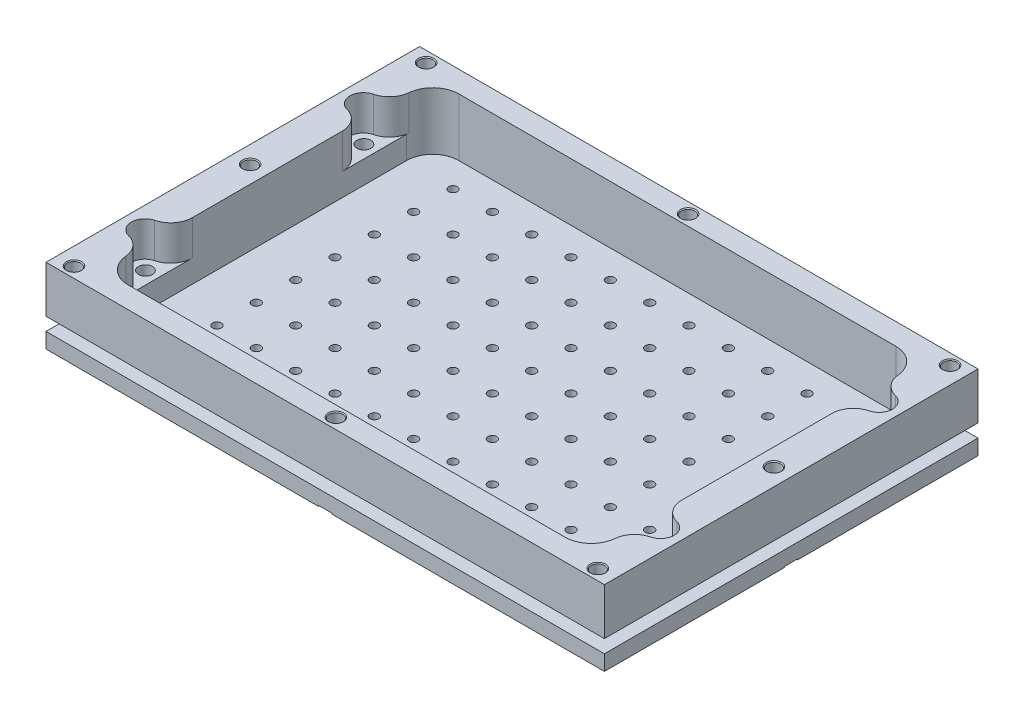
SolidWorks part; units mm, degrees
material "Alliage 6061"
ref_plane "Plan de face" through (0, 0, 0) normal (0, 0, 1) x (1, 0, 0)
ref_plane "Plan de dessus" through (0, 0, 0) normal (0, 1, 0) x (1, 0, 0)
ref_plane "Plan de droite" through (0, 0, 0) normal (1, 0, 0) x (0, 0, -1)
sketch "Esquisse1" plane through (0, 0, 0) normal (0, 1, 0) x (1, 0, 0)
  line L1 (-63.88, 42.74) -> (63.88, 42.74)
  line L2 (-63.88, 42.74) -> (-63.88, -42.74)
  line L3 (-63.88, -42.74) -> (63.88, -42.74)
  line L4 (63.88, 42.74) -> (63.88, -42.74)
  line L5 (-63.88, 42.74) -> (63.88, -42.74) construction
  line L6 (-63.88, -42.74) -> (63.88, 42.74) construction
  point P0 (0, 0)
  dimension "D1" = 85.48
  dimension "D2" = 127.76
extrude "Boss.-Extru.1" add sketch "Esquisse1" along normal blind 12
sketch "Esquisse2" plane through (0, 12, 0) normal (0, 1, 0) x (1, 0, 0)
  line L1 (-49.98, 37.84) -> (49.98, 37.84)
  line L2 (-55.98, 31.84) -> (-55.98, -31.84)
  line L3 (-49.98, -37.84) -> (49.98, -37.84)
  line L4 (55.98, 31.84) -> (55.98, -31.84)
  line L5 (-55.98, 37.84) -> (55.98, -37.84) construction
  line L6 (-55.98, -37.84) -> (55.98, 37.84) construction
  line L7 (-63.88, 42.74) -> (-63.88, -42.74) construction
  arc A0 (-55.98, -31.84) -> (-49.98, -37.84) centre (-49.98, -31.84) ccw
  arc A1 (49.98, -37.84) -> (55.98, -31.84) centre (49.98, -31.84) ccw
  arc A2 (49.98, 37.84) -> (55.98, 31.84) centre (49.98, 31.84) cw
  arc A3 (-49.98, 37.84) -> (-55.98, 31.84) centre (-49.98, 31.84) ccw
  point P0 (0, 0)
  dimension "D3" = 6
  dimension "D1" = 75.68
  dimension "D2" = 7.9
extrude "Enlèv. mat.-Extru.1" cut sketch "Esquisse2" against normal blind 8
ref_plane "Plan1" through (0, 3.5, 0) normal (0, -1, 0) x (-1, 0, 0)
sketch "Esquisse3" plane through (0, 3.5, 0) normal (0, -1, 0) x (-1, 0, 0)
  line L0 (63.88, 42.74) -> (63.88, -42.74) construction
  line L1 (-60.88, 39.74) -> (60.88, 39.74)
  line L2 (-60.88, 39.74) -> (-60.88, -39.74)
  line L3 (-60.88, -39.74) -> (60.88, -39.74)
  line L4 (60.88, 39.74) -> (60.88, -39.74)
  line L5 (-60.88, 39.74) -> (60.88, -39.74) construction
  line L6 (-60.88, -39.74) -> (60.88, 39.74) construction
  line L7 (-63.88, 42.74) -> (63.88, 42.74) construction
  point P0 (0, 0)
  dimension "D1" = 3
  dimension "D2" = 3
extrude "Enlèv. de mat.-Extru.-Mince1" cut sketch "Esquisse3" against normal blind 3 thin thin type one direction wall 10
sketch "Esquisse5" plane through (0, 12, 0) normal (0, 1, 0) x (1, 0, 0)
  line L2 (63.88, 42.74) -> (-63.88, 42.74) construction
  line L4 (-63.88, 42.74) -> (-63.88, -42.74) construction
  circle A0 centre (-45, 31.5) radius 1
  circle A1 centre (-36, 31.5) radius 1
  circle A2 centre (-27, 31.5) radius 1
  circle A3 centre (-18, 31.5) radius 1
  circle A4 centre (-9, 31.5) radius 1
  circle A5 centre (0, 31.5) radius 1
  circle A6 centre (9, 31.5) radius 1
  circle A7 centre (18, 31.5) radius 1
  circle A8 centre (27, 31.5) radius 1
  circle A9 centre (36, 31.5) radius 1
  circle A10 centre (45, 31.5) radius 1
  circle A12 centre (-36, 22.5) radius 1
  circle A13 centre (-27, 22.5) radius 1
  circle A14 centre (-18, 22.5) radius 1
  circle A15 centre (-9, 22.5) radius 1
  circle A16 centre (0, 22.5) radius 1
  circle A17 centre (9, 22.5) radius 1
  circle A18 centre (18, 22.5) radius 1
  circle A19 centre (27, 22.5) radius 1
  circle A20 centre (36, 22.5) radius 1
  circle A21 centre (45, 22.5) radius 1
  circle A23 centre (-36, 13.5) radius 1
  circle A24 centre (-27, 13.5) radius 1
  circle A25 centre (-18, 13.5) radius 1
  circle A26 centre (-9, 13.5) radius 1
  circle A27 centre (0, 13.5) radius 1
  circle A28 centre (9, 13.5) radius 1
  circle A29 centre (18, 13.5) radius 1
  circle A30 centre (27, 13.5) radius 1
  circle A31 centre (36, 13.5) radius 1
  circle A32 centre (45, 13.5) radius 1
  circle A34 centre (-36, 4.5) radius 1
  circle A35 centre (-27, 4.5) radius 1
  circle A36 centre (-18, 4.5) radius 1
  circle A37 centre (-9, 4.5) radius 1
  circle A38 centre (0, 4.5) radius 1
  circle A39 centre (9, 4.5) radius 1
  circle A40 centre (18, 4.5) radius 1
  circle A41 centre (27, 4.5) radius 1
  circle A42 centre (36, 4.5) radius 1
  circle A43 centre (45, 4.5) radius 1
  circle A45 centre (-36, -4.5) radius 1
  circle A46 centre (-27, -4.5) radius 1
  circle A47 centre (-18, -4.5) radius 1
  circle A48 centre (-9, -4.5) radius 1
  circle A49 centre (0, -4.5) radius 1
  circle A50 centre (9, -4.5) radius 1
  circle A51 centre (18, -4.5) radius 1
  circle A52 centre (27, -4.5) radius 1
  circle A53 centre (36, -4.5) radius 1
  circle A54 centre (45, -4.5) radius 1
  circle A56 centre (-36, -13.5) radius 1
  circle A57 centre (-27, -13.5) radius 1
  circle A58 centre (-18, -13.5) radius 1
  circle A59 centre (-9, -13.5) radius 1
  circle A60 centre (0, -13.5) radius 1
  circle A61 centre (9, -13.5) radius 1
  circle A62 centre (18, -13.5) radius 1
  circle A63 centre (27, -13.5) radius 1
  circle A64 centre (36, -13.5) radius 1
  circle A65 centre (45, -13.5) radius 1
  circle A67 centre (-36, -22.5) radius 1
  circle A68 centre (-27, -22.5) radius 1
  circle A69 centre (-18, -22.5) radius 1
  circle A70 centre (-9, -22.5) radius 1
  circle A71 centre (0, -22.5) radius 1
  circle A72 centre (9, -22.5) radius 1
  circle A73 centre (18, -22.5) radius 1
  circle A74 centre (27, -22.5) radius 1
  circle A75 centre (36, -22.5) radius 1
  circle A76 centre (45, -22.5) radius 1
  circle A78 centre (-36, -31.5) radius 1
  circle A79 centre (-27, -31.5) radius 1
  circle A80 centre (-18, -31.5) radius 1
  circle A81 centre (-9, -31.5) radius 1
  circle A82 centre (0, -31.5) radius 1
  circle A83 centre (9, -31.5) radius 1
  circle A84 centre (18, -31.5) radius 1
  circle A85 centre (27, -31.5) radius 1
  circle A86 centre (36, -31.5) radius 1
  circle A87 centre (45, -31.5) radius 1
  circle A89 centre (-45, 22.5) radius 1
  circle A90 centre (-45, 13.5) radius 1
  circle A91 centre (-45, 4.5) radius 1
  circle A92 centre (-45, -4.5) radius 1
  circle A93 centre (-45, -13.5) radius 1
  circle A94 centre (-45, -22.5) radius 1
  circle A95 centre (-45, -31.5) radius 1
  circle A96 centre (54, 31.5) radius 1 [skipped]
  circle A97 centre (54, 22.5) radius 1 [skipped]
  circle A98 centre (54, 13.5) radius 1 [skipped]
  circle A99 centre (54, 4.5) radius 1 [skipped]
  circle A100 centre (54, -4.5) radius 1 [skipped]
  circle A101 centre (54, -13.5) radius 1 [skipped]
  circle A102 centre (54, -22.5) radius 1 [skipped]
  circle A103 centre (54, -31.5) radius 1 [skipped]
  dimension "D1" = 2
  dimension "D2" = 11.24
  dimension "D3" = 18.88
  dimension "D6" = 9
  dimension "D7" = 9
  dimension "D4" = 12
  dimension "D5" = 8
extrude "Enlèv. mat.-Extru.2" cut sketch "Esquisse5" against normal through all
sketch "Esquisse6" plane through (0, 12, 0) normal (0, 1, 0) x (1, 0, 0)
  line L1 (-55.88, 37.84) -> (55.88, 37.84)
  line L2 (-61.88, 31.84) -> (-61.88, -31.84)
  line L3 (-55.88, -37.84) -> (55.88, -37.84)
  line L4 (61.88, 31.84) -> (61.88, -31.84)
  line L5 (-61.88, 37.84) -> (61.88, -37.84) construction
  line L6 (-61.88, -37.84) -> (61.88, 37.84) construction
  line L7 (-63.88, 42.74) -> (-63.88, -42.74) construction
  arc A0 (-61.88, -31.84) -> (-55.88, -37.84) centre (-55.88, -31.84) ccw
  arc A1 (55.88, -37.84) -> (61.88, -31.84) centre (55.88, -31.84) ccw
  arc A2 (55.88, 37.84) -> (61.88, 31.84) centre (55.88, 31.84) cw
  arc A3 (-55.88, 37.84) -> (-61.88, 31.84) centre (-55.88, 31.84) ccw
  point P0 (0, 0)
  dimension "D3" = 6
  dimension "D1" = 2
  dimension "D2" = 75.68
extrude "Enlèv. mat.-Extru.3" cut sketch "Esquisse6" against normal blind 2.8
sketch "Esquisse11" plane through (-60.88, 0, 0) normal (-1, 0, 0) x (0, 0, 1)
  line L0 (-39.74, 6.5) -> (-43.99, 6.5)
  line L1 (-43.99, 6.5) -> (-41.49, 19.5)
  line L2 (-46.49, -11.4642) -> (-46.49, 18.5) construction
  line L3 (-39.74, 6.5) -> (-39.74, 3.5) construction
  dimension "D1" = 6.75
  dimension "D2" = 5
  dimension "D3" = 10
  dimension "D4" = 13
sketch "Esquisse12" plane through (0, 6.5, 0) normal (0, -1, 0) x (-1, 0, 0)
  line L0 (-60.88, -39.74) -> (-63.88, -42.74)
sketch "Esquisse15" plane through (0, 0, 0) normal (0, -1, 0) x (-1, 0, 0)
  line L0 (36, 24) -> (1.5, 24)
  line L1 (45, -33) -> (1.5, -33)
  line L2 (46.5, -31.5) -> (46.5, -1.5)
  line L3 (45, 33) -> (1.5, 33)
  line L4 (-46.5, -31.5) -> (-46.5, -1.5)
  line L5 (46.5, -33) -> (-46.5, 33) construction
  line L6 (46.5, 33) -> (-46.5, -33) construction
  line L7 (43.5, -30) -> (1.5, -30)
  line L8 (43.5, -30) -> (43.5, -1.5)
  line L9 (43.5, 30) -> (1.5, 30)
  line L10 (-43.5, -30) -> (-43.5, -1.5)
  line L11 (43.5, -30) -> (-43.5, 30) construction
  line L12 (43.5, 30) -> (-43.5, -30) construction
  line L13 (-37.5, -22.5) -> (-37.5, -1.5)
  line L14 (36, -24) -> (1.5, -24)
  line L15 (37.5, -22.5) -> (37.5, -1.5)
  line L16 (34.5, 21) -> (1.5, 21)
  line L17 (-34.5, -21) -> (-34.5, -1.5)
  line L18 (34.5, -21) -> (1.5, -21)
  line L19 (34.5, -21) -> (34.5, -1.5)
  line L20 (-25.5, -12) -> (-25.5, -1.5)
  line L21 (25.5, 12) -> (1.5, 12)
  line L22 (25.5, -12) -> (25.5, -1.5)
  line L23 (25.5, -12) -> (1.5, -12)
  line L24 (-28.5, -13.5) -> (-28.5, -1.5)
  line L25 (27, 15) -> (1.5, 15)
  line L26 (28.5, -13.5) -> (28.5, -1.5)
  line L27 (27, -15) -> (1.5, -15)
  line L32 (-19.5, -4.5) -> (-19.5, -1.5)
  line L33 (18, 6) -> (1.5, 6)
  line L34 (19.5, -4.5) -> (19.5, -1.5)
  line L35 (18, -6) -> (1.5, -6)
  line L36 (-63.88, 1.5) -> (-46.5, 1.5)
  line L37 (-63.88, -42.74) -> (-63.88, 42.74) construction
  line L38 (-63.88, -1.5) -> (-46.5, -1.5)
  line L39 (-63.88, 0) -> (63.88, 0) construction
  line L40 (63.88, 42.74) -> (63.88, -42.74) construction
  line L41 (0, 42.74) -> (0, -42.74) construction
  line L42 (-63.88, 42.74) -> (63.88, 42.74) construction
  line L43 (63.88, -42.74) -> (-63.88, -42.74) construction
  line L44 (-1.5, 42.74) -> (-1.5, 33)
  line L45 (1.5, 42.74) -> (1.5, 33)
  line L46 (-1.5, 42.74) -> (1.5, 42.74)
  line L47 (63.88, 1.5) -> (63.88, -1.5)
  line L48 (-63.88, 1.5) -> (-63.88, -1.5)
  line L49 (-1.5, -42.74) -> (1.5, -42.74)
  line L50 (1.5, 30) -> (1.5, 24)
  line L51 (-1.5, 30) -> (-1.5, 24)
  line L52 (-1.5, 33) -> (-45, 33)
  line L53 (-1.5, 30) -> (-43.5, 30)
  line L54 (46.5, 33) -> (-46.5, 33) construction
  line L55 (-1.5, 24) -> (-36, 24)
  line L56 (43.5, 30) -> (-43.5, 30) construction
  line L57 (1.5, 21) -> (1.5, 15)
  line L58 (37.5, 24) -> (-37.5, 24) construction
  line L59 (-1.5, 21) -> (-1.5, 15)
  line L60 (-1.5, 21) -> (-34.5, 21)
  line L61 (-1.5, 15) -> (-27, 15)
  line L62 (34.5, 21) -> (-34.5, 21) construction
  line L63 (-1.5, 12) -> (-25.5, 12)
  line L64 (28.5, 15) -> (-28.5, 15) construction
  line L65 (1.5, 12) -> (1.5, 6)
  line L66 (25.5, 12) -> (-25.5, 12) construction
  line L67 (-1.5, 12) -> (-1.5, 6)
  line L68 (-1.5, 6) -> (-18, 6)
  line L70 (19.5, 6) -> (-19.5, 6) construction
  line L72 (46.5, 1.5) -> (46.5, 31.5)
  line L75 (-1.5, -6) -> (-1.5, -12)
  line L76 (1.5, -6) -> (1.5, -12)
  line L80 (-1.5, -6) -> (-18, -6)
  line L81 (-1.5, -12) -> (-25.5, -12)
  line L82 (19.5, -6) -> (-19.5, -6) construction
  line L83 (-1.5, -15) -> (-27, -15)
  line L84 (25.5, -12) -> (-25.5, -12) construction
  line L85 (-1.5, -15) -> (-1.5, -21)
  line L86 (28.5, -15) -> (-28.5, -15) construction
  line L87 (1.5, -15) -> (1.5, -21)
  line L88 (-1.5, -21) -> (-34.5, -21)
  line L89 (-1.5, -24) -> (-36, -24)
  line L90 (34.5, -21) -> (-34.5, -21) construction
  line L91 (-1.5, -24) -> (-1.5, -30)
  line L92 (37.5, -24) -> (-37.5, -24) construction
  line L93 (1.5, -24) -> (1.5, -30)
  line L94 (1.5, -33) -> (1.5, -42.74)
  line L95 (-1.5, -33) -> (-1.5, -42.74)
  line L96 (-1.5, -30) -> (-43.5, -30)
  line L97 (-1.5, -33) -> (-45, -33)
  line L98 (43.5, -30) -> (-43.5, -30) construction
  line L99 (-43.5, 1.5) -> (-43.5, 30)
  line L100 (46.5, -33) -> (-46.5, -33) construction
  line L101 (-46.5, 1.5) -> (-46.5, 31.5)
  line L102 (-43.5, -30) -> (-43.5, 30) construction
  line L103 (-43.5, 1.5) -> (-37.5, 1.5)
  line L104 (-46.5, -33) -> (-46.5, 33) construction
  line L105 (-43.5, -1.5) -> (-37.5, -1.5)
  line L106 (-34.5, 1.5) -> (-28.5, 1.5)
  line L107 (-34.5, -1.5) -> (-28.5, -1.5)
  line L108 (-25.5, 1.5) -> (-19.5, 1.5)
  line L109 (-25.5, -1.5) -> (-19.5, -1.5)
  line L112 (-25.5, 1.5) -> (-25.5, 12)
  line L113 (-28.5, 1.5) -> (-28.5, 13.5)
  line L114 (-25.5, -12) -> (-25.5, 12) construction
  line L115 (-34.5, 1.5) -> (-34.5, 21)
  line L116 (-28.5, -15) -> (-28.5, 15) construction
  line L117 (-37.5, 1.5) -> (-37.5, 22.5)
  line L118 (-34.5, -21) -> (-34.5, 21) construction
  line L119 (-19.5, 1.5) -> (-19.5, 4.5)
  line L120 (-37.5, -24) -> (-37.5, 24) construction
  line L122 (-19.5, -6) -> (-19.5, 6) construction
  line L123 (-1.5, -1.0345) -> (-1.5, -1.0645)
  line L125 (-1.5, 1.0645) -> (-1.5, 1.0345)
  line L128 (1.5, -1.0345) -> (1.5, -1.0645)
  line L129 (1.5, 1.0645) -> (1.5, 1.0345)
  line L131 (19.5, 1.5) -> (19.5, 4.5)
  line L133 (25.5, 1.5) -> (25.5, 12)
  line L134 (19.5, -6) -> (19.5, 6) construction
  line L135 (28.5, 1.5) -> (28.5, 13.5)
  line L136 (25.5, -12) -> (25.5, 12) construction
  line L137 (34.5, 1.5) -> (34.5, 21)
  line L138 (28.5, -15) -> (28.5, 15) construction
  line L139 (37.5, 1.5) -> (37.5, 22.5)
  line L140 (34.5, -21) -> (34.5, 21) construction
  line L141 (43.5, 1.5) -> (43.5, 30)
  line L142 (37.5, -24) -> (37.5, 24) construction
  line L143 (37.5, 1.5) -> (43.5, 1.5)
  line L144 (43.5, -30) -> (43.5, 30) construction
  line L145 (28.5, 1.5) -> (34.5, 1.5)
  line L146 (28.5, -1.5) -> (34.5, -1.5)
  line L147 (19.5, 1.5) -> (25.5, 1.5)
  line L148 (19.5, -1.5) -> (25.5, -1.5)
  line L149 (37.5, -1.5) -> (43.5, -1.5)
  line L150 (46.5, 1.5) -> (63.88, 1.5)
  line L151 (46.5, -1.5) -> (63.88, -1.5)
  line L152 (46.5, -33) -> (46.5, 33) construction
  arc A0 (-28.5, -13.5) -> (-27, -15) centre (-27, -13.5) ccw
  circle A1 centre (-45, 31.5) radius 1 construction
  circle A2 centre (-45, 22.5) radius 1 construction
  arc A3 (27, 15) -> (28.5, 13.5) centre (27, 13.5) cw
  arc A4 (-28.5, 13.5) -> (-27, 15) centre (-27, 13.5) cw
  arc A5 (-19.5, -4.5) -> (-18, -6) centre (-18, -4.5) ccw
  arc A6 (-19.5, 4.5) -> (-18, 6) centre (-18, 4.5) cw
  arc A7 (18, 6) -> (19.5, 4.5) centre (18, 4.5) cw
  arc A8 (19.5, -4.5) -> (18, -6) centre (18, -4.5) cw
  arc A9 (28.5, -13.5) -> (27, -15) centre (27, -13.5) cw
  arc A10 (36, -24) -> (37.5, -22.5) centre (36, -22.5) ccw
  arc A11 (36, 24) -> (37.5, 22.5) centre (36, 22.5) cw
  arc A12 (-36, 24) -> (-37.5, 22.5) centre (-36, 22.5) ccw
  arc A13 (-37.5, -22.5) -> (-36, -24) centre (-36, -22.5) ccw
  arc A14 (-45, -33) -> (-46.5, -31.5) centre (-45, -31.5) cw
  arc A15 (45, -33) -> (46.5, -31.5) centre (45, -31.5) ccw
  arc A16 (46.5, 31.5) -> (45, 33) centre (45, 31.5) ccw
  arc A17 (-45, 33) -> (-46.5, 31.5) centre (-45, 31.5) ccw
  point P0 (0, 0)
  point P2 (0, 0)
  point P31 (-16.5, -3)
  point P32 (-16.5, 3)
  point P33 (16.5, 3)
  point P34 (16.5, -3)
  dimension "D1" = 1.5
  dimension "D5" = 9
  dimension "D12" = 1.5
  dimension "D2" = 1.5
  dimension "D3" = 3
  dimension "D4" = 3
  dimension "D8" = 1.5
  dimension "D9" = 3
  dimension "D10" = 3
  dimension "D11" = 1.5
  dimension "D6" = 9
  dimension "D7" = 9
extrude "Enlèv. mat.-Extru.4" cut sketch "Esquisse15" against normal blind 0.2 contours L101 L36 L48 L38 L4 L97 L95 L49 L94 L1 L2 L3 L45 L46 L44 L52 L147 L131 L33 L65 L21 L133 L145 L135 L25 L57 L16 L137 L143 L139 L0 L50 L9 L141 region at (0, 0, 0)
sketch "Esquisse16" plane through (0, 9.2, 0) normal (0, 1, 0) x (1, 0, 0)
  line L16 (49.98, 37.84) -> (-49.98, 37.84) construction
  line L17 (55.98, -31.84) -> (55.98, 31.84) construction
  line L18 (-49.98, -37.84) -> (49.98, -37.84) construction
  line L19 (-55.98, 31.84) -> (-55.98, -31.84) construction
  line L20 (-63.88, 42.74) -> (-63.88, -42.74) construction
  line L21 (63.88, 42.74) -> (-63.88, 42.74) construction
  line L22 (63.88, -42.74) -> (63.88, 42.74) construction
  line L23 (-63.88, -42.74) -> (63.88, -42.74) construction
  line L24 (-63.88, -42.74) -> (63.88, -42.74)
  line L25 (63.88, -42.74) -> (63.88, 42.74)
  line L26 (63.88, 42.74) -> (-63.88, 42.74)
  line L27 (-63.88, 42.74) -> (-63.88, -42.74)
  line L28 (-55.98, 31.84) -> (-55.98, -31.84)
  line L29 (-49.98, -37.84) -> (49.98, -37.84)
  line L30 (55.98, -31.84) -> (55.98, 31.84)
  line L31 (49.98, 37.84) -> (-49.98, 37.84)
  arc A26 (-49.98, 37.84) -> (-55.98, 31.84) centre (-49.98, 31.84) ccw construction
  arc A27 (55.98, 31.84) -> (49.98, 37.84) centre (49.98, 31.84) ccw construction
  arc A28 (49.98, -37.84) -> (55.98, -31.84) centre (49.98, -31.84) ccw construction
  arc A29 (-55.98, -31.84) -> (-49.98, -37.84) centre (-49.98, -31.84) ccw construction
  arc A30 (-55.98, -31.84) -> (-49.98, -37.84) centre (-49.98, -31.84) ccw
  arc A31 (49.98, -37.84) -> (55.98, -31.84) centre (49.98, -31.84) ccw
  arc A32 (55.98, 31.84) -> (49.98, 37.84) centre (49.98, 31.84) ccw
  arc A33 (-49.98, 37.84) -> (-55.98, 31.84) centre (-49.98, 31.84) ccw
extrude "Boss.-Extru.2" add sketch "Esquisse16" along normal blind 8
sketch "Esquisse18" plane through (0, 17.2, 0) normal (0, 1, 0) x (1, 0, 0)
  line L0 (0, 55.6406) -> (0, -55.6406) construction
  line L1 (-114.8615, 0) -> (114.8615, 0) construction
  line L2 (55.98, -21.9) -> (58.98, -21.9)
  line L3 (55.98, -31.84) -> (55.98, 31.84) construction
  line L5 (58.98, -28.1) -> (55.98, -28.1)
  line L6 (55.98, -28.1) -> (55.98, -21.9)
  line L8 (-55.98, -28.1) -> (-55.98, -21.9)
  line L9 (-58.98, -28.1) -> (-55.98, -28.1)
  line L10 (-55.98, -21.9) -> (-58.98, -21.9)
  line L11 (-55.98, 21.9) -> (-58.98, 21.9)
  line L12 (-58.98, 28.1) -> (-55.98, 28.1)
  line L13 (-55.98, 28.1) -> (-55.98, 21.9)
  line L14 (55.98, 28.1) -> (55.98, 21.9)
  line L15 (58.98, 28.1) -> (55.98, 28.1)
  line L16 (55.98, 21.9) -> (58.98, 21.9)
  arc A0 (58.98, -21.9) -> (58.98, -28.1) centre (58.98, -25) cw
  arc A1 (-58.98, -21.9) -> (-58.98, -28.1) centre (-58.98, -25) ccw
  arc A2 (-58.98, 21.9) -> (-58.98, 28.1) centre (-58.98, 25) cw
  arc A3 (58.98, 21.9) -> (58.98, 28.1) centre (58.98, 25) ccw
  point P7 (55.98, -25)
  point P24 (0, 0)
  point P26 (0, 0)
  dimension "D5" = 58.98
  dimension "D3" = 6.2
  dimension "D4" = 25
extrude "Enlèv. mat.-Extru.5" cut sketch "Esquisse18" against normal blind 8
hole_wizard "Fraisage pour vis à tête fraisée à 6 pans creux M31" positions "Esquisse8" profile "Esquisse9" countersink size "M3" standard "ISO" end condition through all
sketch "Esquisse8" plane through (0, 0, 0) normal (0, -1, 0) x (-1, 0, 0)
  line L4 (-63.88, -42.74) -> (-63.88, -1.5) construction
  line L5 (0, -8.3856) -> (0, 52.5362) construction
  point P0 (-58.88, 25)
  point P2 (-58.88, -25)
  point P34 (58.88, -25)
  point P35 (58.88, 25)
  dimension "D1" = 5
  dimension "D2" = 50
  dimension "D3" = 25
sketch "Esquisse9" plane through (58.88, 0, -25) normal (1, 0, 0) x (0, 0, -1)
  line L0 (0, 0) -> (0, 17.2)
  line L1 (0, 17.2) -> (1.6, 17.2)
  line L2 (1.6, 17.2) -> (1.6, 1.76)
  line L3 (1.6, 1.76) -> (3.36, 0)
  line L5 (3.36, 0) -> (0, 0)
  line L6 (-1.6, 1.76) -> (-3.36, 0) construction
  line L11 (0, -6.35) -> (0, 107.95) construction
  dimension "Diamètre du perçage jusqu'au prochain" = 3.2
  dimension "Profondeur du perçage jusqu'au prochain" = 17.2
  dimension "Diamètre du fraisage entrant" = 6.72
  dimension "Angle du fraisage entrant" = 90
fillet "Congé1" radius 5 8 edges at (55.98, 13.2, 28.1) (55.98, 13.2, 21.9) (55.98, 13.2, -21.9) (55.98, 13.2, -28.1) (-55.98, 13.2, -21.9) (-55.98, 13.2, 28.1) (-55.98, 13.2, 21.9) (-55.98, 13.2, -28.1)
sketch "Esquisse19" plane through (0, 17.2, 0) normal (0, 1, 0) x (1, 0, 0)
  line L0 (63.88, 42.74) -> (-63.88, 42.74) construction
  line L1 (-29.965, 20.9896) -> (-29.965, 9.5513) construction
  line L2 (-38.7577, 20.145) -> (-23.6533, 20.145) construction
  line L3 (0, -9.5125) -> (0, 11.6044) construction
  line L4 (10.2216, 0) -> (-8.6955, 0) construction
  line L5 (-63.88, 42.74) -> (-63.88, -42.74) construction
  circle A26 centre (-59.93, 40.29) radius 1.55
  circle A27 centre (0, 40.29) radius 1.55
  circle A29 centre (-59.93, 0) radius 1.55
  circle A32 centre (59.93, 0) radius 1.55
  circle A34 centre (59.93, 40.29) radius 1.55
  circle A35 centre (59.93, -40.29) radius 1.55
  circle A40 centre (0, -40.29) radius 1.55
  circle A41 centre (-59.93, -40.29) radius 1.55
  dimension "D1" = 3.95
  dimension "D3" = 3.1
  dimension "D2" = 2.45
extrude "Enlèv. mat.-Extru.6" cut sketch "Esquisse19" against normal blind 3
chamfer "Chanfrein1" distance 0.2 angle 45 8 edges at (-59.93, 17.2, 1.55) (-59.93, 17.2, 38.74) (0, 17.2, 38.74) (59.93, 17.2, 41.84) (59.93, 17.2, -1.55) (59.93, 17.2, -41.84) (0, 17.2, -38.74) (-59.93, 17.2, -38.74)
sketch "Esquisse20" plane through (0, 14.2, 0) normal (0, 1, 0) x (1, 0, 0)
  circle A1 centre (59.93, 40.29) radius 0.75
  circle A2 centre (0, 40.29) radius 0.75
  circle A3 centre (-59.93, 40.29) radius 0.75
  circle A4 centre (-59.93, 0) radius 0.75
  circle A5 centre (-59.93, -40.29) radius 0.75
  circle A6 centre (0, -40.29) radius 0.75
  circle A7 centre (59.93, -40.29) radius 0.75
  circle A8 centre (59.93, 0) radius 0.75
  dimension "D1" = 1.5
extrude "Enlèv. mat.-Extru.7" cut sketch "Esquisse20" against normal blind 2
